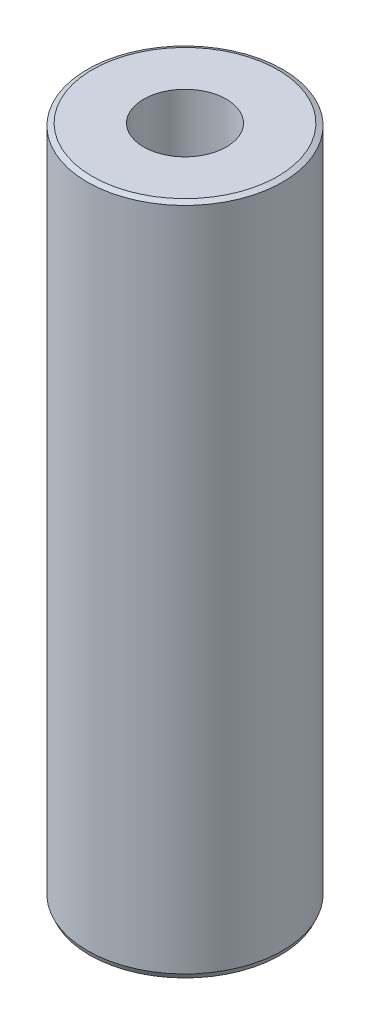
SolidWorks part; units mm, degrees
ref_plane "Front Plane" through (0, 0, 0) normal (0, 0, 1) x (1, 0, 0)
ref_plane "Top Plane" through (0, 0, 0) normal (0, 1, 0) x (1, 0, 0)
ref_plane "Right Plane" through (0, 0, 0) normal (1, 0, 0) x (0, 0, -1)
sketch "Sketch1" plane through (0, 0, 0) normal (0, 1, 0) x (1, 0, 0)
  circle A0 centre (0, 0) radius 27.5
  dimension "SHAFT_OD" = 55
extrude "Boss-Extrude1" add sketch "Sketch1" along normal blind 189.4762
sketch "Sketch2" plane through (0, 0, 0) normal (0, 1, 0) x (1, 0, 0)
  circle A0 centre (0, 0) radius 11.6585
  dimension "BORE_D" = 23.317
extrude "Cut-Extrude1" cut sketch "Sketch2" along normal through all
chamfer "Chamfer1" distance 0.6488 angle 65.636 2 edges at (0, 189.4762, 27.5) (0, 0, 27.5) first distance on face at (0, 189.4762, 27.5) first distance on face at (0, 0, 11.6585)
